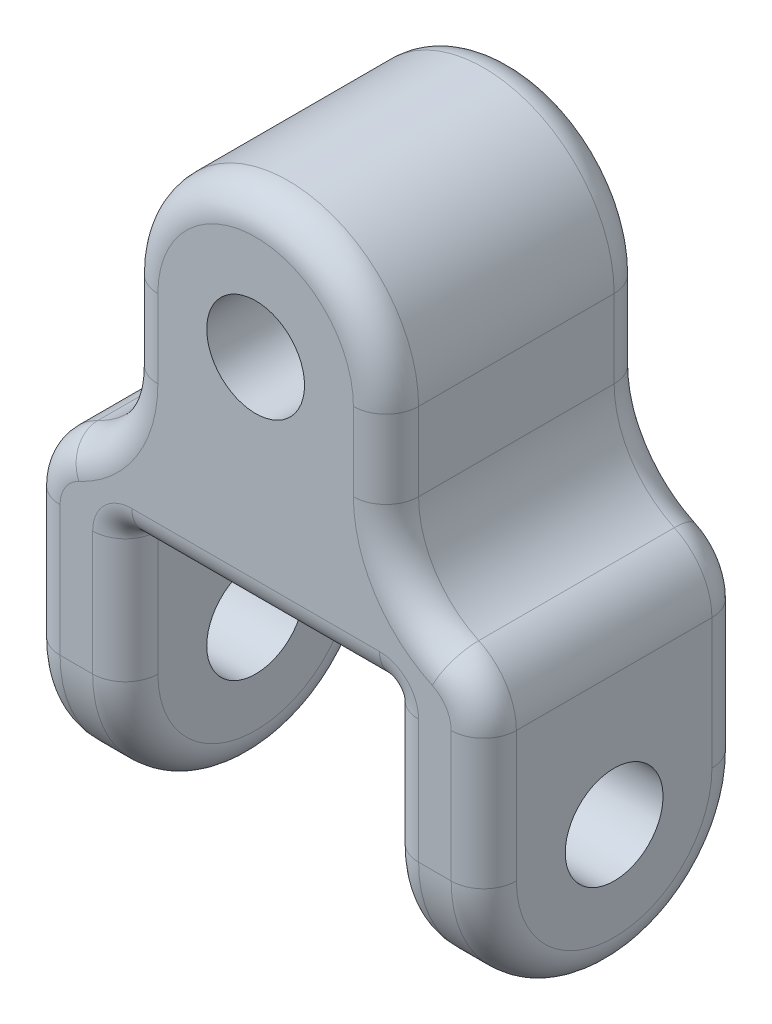
SolidWorks part; units mm, degrees
ref_plane "Front Plane" through (0, 0, 0) normal (0, 0, 1) x (1, 0, 0)
ref_plane "Top Plane" through (0, 0, 0) normal (0, 1, 0) x (1, 0, 0)
ref_plane "Right Plane" through (0, 0, 0) normal (1, 0, 0) x (0, 0, -1)
sketch "Sketch1" plane through (0, 0, 0) normal (0, 0, 1) x (1, 0, 0)
  line L0 (0, 0) -> (0, 103.316) construction
  line L1 (-20, 40) -> (-20, 0)
  line L2 (-20, 0) -> (-35, 0)
  line L3 (-35, 0) -> (-35, 40)
  line L4 (-20, 63.5584) -> (-20, 75.5584)
  line L5 (20, 40) -> (20, 0)
  line L6 (20, 0) -> (35, 0)
  line L7 (35, 0) -> (35, 40)
  line L8 (20, 63.5584) -> (20, 75.5584)
  line L9 (-20, 40) -> (20, 40)
  arc A0 (-35, 40) -> (-29.2308, 49.0609) centre (-25, 40) cw
  arc A1 (-29.2308, 49.0609) -> (-20, 63.5584) centre (-36, 63.5584) ccw
  arc A2 (-20, 75.5584) -> (20, 75.5584) centre (0, 75.5584) cw
  arc A3 (35, 40) -> (29.2308, 49.0609) centre (25, 40) ccw
  arc A4 (29.2308, 49.0609) -> (20, 63.5584) centre (36, 63.5584) cw
  dimension "D4" = 10
  dimension "D5" = 16
  dimension "D7" = 20
  dimension "D1" = 20
  dimension "D2" = 15
  dimension "D3" = 40
  dimension "D6" = 12
  dimension "D9" = 40
extrude "Boss-Extrude1" add sketch "Sketch1" along normal blind 40
fillet "Fillet2" 2 edges at (27.5, 0, 40) (27.5, 0, 0) type full round first side face at (0, 39.6677, 40) second side face at (0, 39.6677, 0) middle face at (27.5, 0, 20)
fillet "Fillet3" 2 edges at (-27.5, 0, 40) (-27.5, 0, 0) type full round first side face at (0, 42.5248, 40) second side face at (0, 42.5248, 0) middle face at (-27.5, 0, 20)
sketch "Sketch2" plane through (-35, 0, 0) normal (-1, 0, 0) x (0, 0, 1)
  circle A0 centre (20, 20) radius 7.5
  dimension "D1" = 15
extrude "Cut-Extrude1" cut sketch "Sketch2" against normal through all
sketch "Sketch3" plane through (0, 0, 40) normal (0, 0, 1) x (1, 0, 0)
  circle A0 centre (0, 74.6025) radius 7.5
  dimension "D1" = 15
extrude "Cut-Extrude2" cut sketch "Sketch3" against normal blind 40
fillet "Fillet5" radius 1 2 edges at (-20, 40, 20) (20, 40, 20)
fillet "Fillet6" radius 5 32 edges at (-33.4353, 45.3709, 40) (-22.5036, 54.9651, 40) (-20, 69.5584, 40) (0, 95.5584, 40) (20, 69.5584, 40) (22.5036, 54.9651, 40) (33.4353, 45.3709, 40) (35, 30, 40) (35, 0, 20) (35, 30, 0) (33.4353, 45.3709, 0) (22.5036, 54.9651, 0) (20, 69.5584, 0) (0, 95.5584, 0) (-20, 69.5584, 0) (-22.5036, 54.9651, 0) (-33.4353, 45.3709, 0) (-35, 30, 0) (-35, 0, 20) (-20, 29.5, 40) (-19.7071, 39.7071, 40) (0, 40, 40) (19.7071, 39.7071, 40) (20, 29.5, 40) (20, 0, 20) (20, 29.5, 0) (19.7071, 39.7071, 0) (0, 40, 0) (-19.7071, 39.7071, 0) (-20, 29.5, 0) (-35, 30, 40) (-20, 0, 20)
